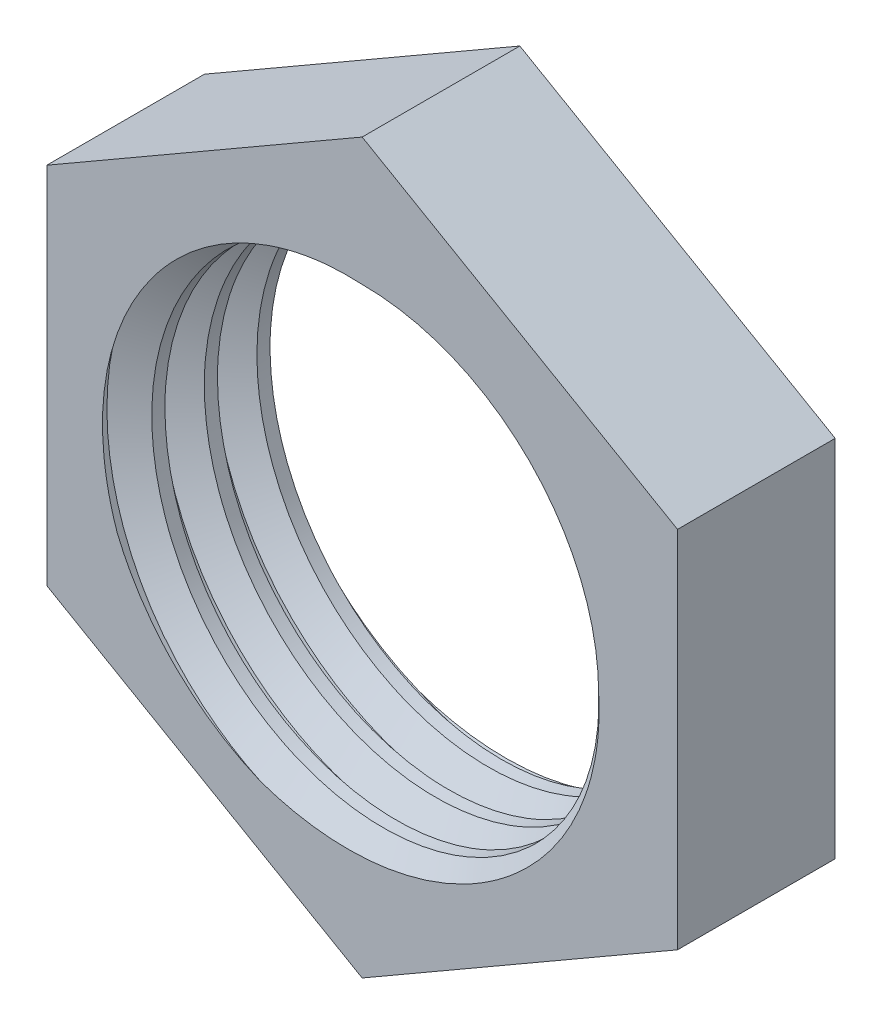
SolidWorks part; units mm, degrees
ref_plane "Płaszczyzna przednia" through (0, 0, 0) normal (0, 0, 1) x (1, 0, 0)
ref_plane "Płaszczyzna górna" through (0, 0, 0) normal (0, 1, 0) x (1, 0, 0)
ref_plane "Płaszczyzna prawa" through (0, 0, 0) normal (1, 0, 0) x (0, 0, -1)
sketch "Szkic1" plane through (0, 0, 0) normal (0, 0, 1) x (1, 0, 0)
  circle A0 centre (0, 0) radius 4
  circle A1 centre (0, -17.8) radius 4
  circle A2 centre (75, 0) radius 4
  circle A3 centre (75, -17.8) radius 4
  dimension "D1" = 8
  dimension "D2" = 8
  dimension "D4" = 8
  dimension "D5" = 8
  dimension "D3" = 17.8
  dimension "D6" = 75
  dimension "D7" = 75
  dimension "D8" = 17.8
sketch "Szkic2" plane through (0, 0, 0) normal (0, 0, -1) x (-1, 0, 0)
  line L0 (-75, 4) -> (0, 4)
  line L1 (4, 0) -> (4, -17.8)
  line L2 (-79, 0) -> (-79, -17.8)
  line L3 (-75, -21.8) -> (0, -21.8)
  circle A0 centre (-75, 0) radius 4 construction
  circle A1 centre (0, 0) radius 4 construction
  circle A2 centre (0, -17.8) radius 4 construction
  circle A3 centre (-75, -17.8) radius 4 construction
  arc A4 (-79, 0) -> (-75, 4) centre (-75, 0) cw
  arc A5 (0, 4) -> (4, 0) centre (0, 0) cw
  arc A6 (0, -21.8) -> (4, -17.8) centre (0, -17.8) ccw
  arc A7 (-75, -21.8) -> (-79, -17.8) centre (-75, -17.8) cw
sketch "Szkic3" plane through (0, 0, -5) normal (0, 0, -1) x (-1, 0, 0)
  circle A0 centre (-55.55, -8.9) radius 4.5
  arc A1 (-79, -17.8) -> (-75, -21.8) centre (-75, -17.8) ccw construction
  dimension "D1" = 19.45
  dimension "D2" = 9
sketch "Szkic4" plane through (0, 0, -5) normal (0, 0, -1) x (-1, 0, 0)
  line L0 (-73.4211, 3.6752) -> (-53.7738, -4.7654)
  line L1 (-73.4205, -21.4749) -> (-53.7738, -13.0346)
  line L2 (-76.7413, -14.2303) -> (-57.5229, -4.8555)
  line L3 (-76.7489, -3.5974) -> (-57.5176, -12.9471)
  line L4 (-79, 0) -> (-79, -17.8)
  line L5 (-75, -21.8) -> (0, -21.8)
  line L6 (4, -17.8) -> (4, 0)
  line L7 (0, 4) -> (-75, 4)
  line L8 (-79, 0) -> (-79, -17.8)
  line L9 (-75, -21.8) -> (0, -21.8)
  line L10 (4, -17.8) -> (4, 0)
  line L11 (0, 4) -> (-75, 4)
  line L12 (-0.5977, -21.7551) -> (-56.2224, -13.3495)
  line L13 (0.6679, -13.8562) -> (-54.7986, -4.4632)
  line L14 (0.6679, -3.9438) -> (-54.7986, -13.3368)
  line L15 (-56.2224, -4.4505) -> (-0.5977, 3.9551)
  circle A1 centre (-74.9938, -17.8127) radius 3.9859
  circle A2 centre (-75, 0) radius 4
  circle A3 centre (0, -17.8) radius 4
  arc A4 (-75, 4) -> (-79, 0) centre (-75, 0) ccw
  arc A5 (-79, -17.8) -> (-75, -21.8) centre (-75, -17.8) ccw
  arc A6 (0, -21.8) -> (4, -17.8) centre (0, -17.8) ccw
  arc A7 (4, 0) -> (0, 4) centre (0, 0) ccw
  arc A8 (-75, 4) -> (-79, 0) centre (-75, 0) ccw
  arc A9 (-79, -17.8) -> (-75, -21.8) centre (-75, -17.8) ccw
  arc A10 (0, -21.8) -> (4, -17.8) centre (0, -17.8) ccw
  arc A11 (4, 0) -> (0, 4) centre (0, 0) ccw
  circle A12 centre (-55.55, -8.9) radius 4.5 construction
  circle A13 centre (0, 0) radius 4
  dimension "D1" = 0
sketch "Szkic5" plane through (0, 0, 0) normal (0, 0, 1) x (1, 0, 0)
  circle A0 centre (55.55, -8.9) radius 6
  circle A1 centre (55.55, -8.9) radius 4.5
  dimension "D1" = 9
  dimension "D2" = 12
extrude "Dodanie-wyciągnięcie4" add sketch "Szkic5" against normal blind 3
sketch "Szkic7" plane through (0, 0, 40) normal (0, 0, 1) x (1, 0, 0)
  circle A0 centre (75, -17.8) radius 1
  circle A2 centre (0, -17.8) radius 1
  circle A3 centre (0, 0) radius 1
  dimension "D1" = 2
  dimension "D2" = 2
  dimension "D3" = 2
extrude "Wytnij-wyciągnięcie4" [suppressed] cut sketch "Szkic7" against normal blind 20
thread "Gwint2" pitch 1 method cut profile "Profil gwintu2" start angle 0, offset 1, length 10, pitch 1, diameter 9
ref_plane "Płaszczyzna2" through (60.05, -8.9, -4) normal (0, -1, 0) x (1, 0, 0)
sketch "Profil gwintu2" plane through (60.05, -8.9, -4) normal (0, -1, 0) x (1, 0, 0)
  line L0 (0, 0) -> (0, 1) construction
  line L1 (0, 0) -> (0.5413, 0.3125)
  line L2 (0.5413, 0.3125) -> (0.5413, 0.4375)
  line L3 (0.5413, 0.4375) -> (0, 0.75)
  line L4 (0.5413, 0.375) -> (0, 0.375) construction
  line L11 (0, 0) -> (0, 0.75)
  point P2 (0, 0)
  dimension "Pitch" = 1
  dimension "Profile_Angle" = 60
  dimension "Profile_Land" = 0.125
  dimension "Profile_Height" = 0.5413
sketch "Szkic8" plane through (0, 0, -3) normal (0, 0, -1) x (-1, 0, 0)
  line L1 (-55.55, -15.8282) -> (-49.55, -12.3641)
  line L2 (-49.55, -12.3641) -> (-49.55, -5.4359)
  line L3 (-49.55, -5.4359) -> (-55.55, -1.9718)
  line L4 (-55.55, -1.9718) -> (-61.55, -5.4359)
  line L5 (-61.55, -5.4359) -> (-61.55, -12.3641)
  line L6 (-61.55, -12.3641) -> (-55.55, -15.8282)
  circle A0 centre (-55.55, -8.9) radius 6 construction
  circle A1 centre (-55.55, -8.9) radius 6 construction
  circle M7 centre (-55.55, -8.9) radius 6
extrude "Dodanie-wyciągnięcie5" add sketch "Szkic8" along normal blind 3 from surface contours L5 L6 M7 | L6 L1 M7 | L1 L2 M7 | L2 L3 M7 | L3 L4 M7 | L4 L5 M7 region at (55.55, -15.1014, -3) region at (50.1794, -12.0007, -3) region at (60.9206, -12.0007, -3) region at (50.1794, -5.7993, -3) region at (60.9206, -5.7993, -3) region at (55.55, -2.6986, -3) starting at face at (61.55, -8.9, 0)
sketch "Szkic9" plane through (0, 0, -3) normal (0, 0, -1) x (-1, 0, 0)
  circle A0 centre (-55.55, -8.9) radius 6
  circle A1 centre (-55.55, -8.9) radius 5.7264
extrude "Dodanie-wyciągnięcie6" [suppressed] add sketch "Szkic9" along normal blind 1
